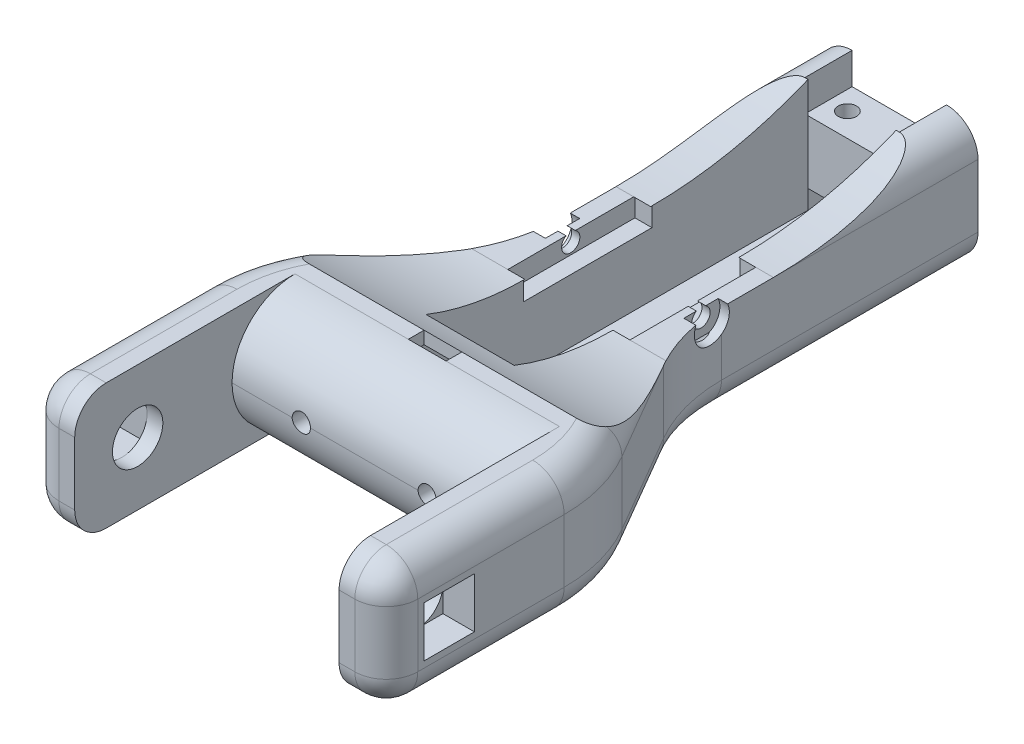
SolidWorks part; units mm, degrees
ref_plane "Спереди" through (0, 0, 0) normal (0, 0, 1) x (1, 0, 0)
ref_plane "Сверху" through (0, 0, 0) normal (0, 1, 0) x (1, 0, 0)
ref_plane "Справа" through (0, 0, 0) normal (1, 0, 0) x (0, 0, -1)
sketch "Эскиз1" plane through (0, 0, 0) normal (0, 1, 0) x (1, 0, 0)
  line L1 (21, 25) -> (-21, 25)
  line L2 (-21, 25) -> (-21, 0)
  line L3 (-21, 0) -> (-28.5, 0)
  line L4 (-28.5, 0) -> (-28.5, 35)
  line L5 (-28.5, 35) -> (-12.5, 62.5)
  line L6 (-12.5, 62.5) -> (-12.5, 110)
  line L7 (-12.5, 110) -> (12.5, 110)
  line L12 (0, -1000) -> (0, 49000) construction
  line L13 (12.5, 62.5) -> (12.5, 110)
  line L14 (28.5, 35) -> (12.5, 62.5)
  line L15 (28.5, 0) -> (28.5, 35)
  line L16 (21, 0) -> (28.5, 0)
  line L17 (21, 25) -> (21, 0)
  point P13 (-24.75, 0)
  point P15 (0, 110)
  point P16 (0, 25)
  dimension "D1" = 21
  dimension "D2" = 7.5
  dimension "D3" = 25
  dimension "D4" = 10
  dimension "D5" = 110
  dimension "D6" = 12.5
  dimension "D7" = 47.5
extrude "Бобышка-Вытянуть1" add sketch "Эскиз1" along normal blind 20
sketch "Эскиз2" plane through (28.5, 0, 0) normal (1, 0, 0) x (0, 0, -1)
  line L0 (-1000, 10) -> (49000, 10) construction
  line L1 (0, 20) -> (0, 0) construction
  line L2 (10, -980) -> (10, 49020) construction
  circle A0 centre (10, 10) radius 4
  point P5 (0, 10)
  dimension "D1" = 8
  dimension "D2" = 10
extrude "Вырез-Вытянуть1" cut sketch "Эскиз2" against normal blind 52
fillet "Скругление1" radius 25 4 edges at (-28.5, 10, -35) (-12.5, 10, -62.5) (28.5, 10, -35) (12.5, 10, -62.5)
fillet "Скругление2" radius 5 26 edges at (-28.5, 20, -14.1282) (-27.6373, 20, -34.7673) (-20.5, 20, -48.75) (-13.3627, 20, -62.7327) (-28.5, 0, -14.1282) (-27.6373, 0, -34.7673) (-20.5, 0, -48.75) (-13.3627, 0, -62.7327) (28.5, 0, -14.1282) (27.6373, 0, -34.7673) (20.5, 0, -48.75) (13.3627, 0, -62.7327) (28.5, 20, -14.1282) (27.6373, 20, -34.7673) (20.5, 20, -48.75) (13.3627, 20, -62.7327) (-24.75, 0, 0) (-24.75, 20, 0) (-28.5, 10, 0) (-12.5, 20, -89.6218) (-12.5, 0, -89.6218) (28.5, 10, 0) (24.75, 0, 0) (24.75, 20, 0) (12.5, 0, -89.6218) (12.5, 20, -89.6218)
fillet "Скругление3" radius 10 2 edges at (0, 0, -25) (0, 20, -25)
sketch "Эскиз4" plane through (28.5, 0, 0) normal (1, 0, 0) x (0, 0, -1)
  line L1 (6, 6) -> (14, 6)
  line L2 (6, 6) -> (6, 14)
  line L3 (6, 14) -> (14, 14)
  line L4 (14, 6) -> (14, 14)
  line L5 (6, 6) -> (14, 14) construction
  line L6 (6, 14) -> (14, 6) construction
  point P0 (10, 10)
  dimension "D1" = 8
extrude "Вырез-Вытянуть2" cut sketch "Эскиз4" against normal blind 5
extrude "Вырез-Вытянуть3" cut sketch "Эскиз4<2>" along normal blind 5 from vertex starting at point (-28.5, 5, -5)
sketch "Эскиз4<2>" plane through (28.5, 0, 0) normal (1, 0, 0) x (0, 0, -1) same geometry as "Эскиз4"
sketch "Эскиз5" plane through (0, 0, -110) normal (0, 0, -1) x (-1, 0, 0)
  line L1 (-7.5, 20) -> (7.5, 20)
  line L2 (-7.5, 20) -> (-7.5, 15)
  line L3 (-7.5, 15) -> (7.5, 15)
  line L4 (7.5, 20) -> (7.5, 15)
  line L5 (-7.5, 0) -> (7.5, 0)
  line L6 (-7.5, 0) -> (-7.5, 5)
  line L7 (-7.5, 5) -> (7.5, 5)
  line L8 (7.5, 0) -> (7.5, 5)
  dimension "D1" = 5
  dimension "D2" = 5
extrude "Вырез-Вытянуть4" cut sketch "Эскиз5" against normal blind 7.5
sketch "Эскиз6" plane through (0, 15, 0) normal (0, 1, 0) x (1, 0, 0)
  line L0 (-1007.5, 106.25) -> (48992.5, 106.25) construction
  line L1 (-7.5, 102.5) -> (-7.5, 110) construction
  line L2 (0, -880) -> (0, 49120) construction
  line L3 (7.5, 110) -> (-7.5, 110) construction
  line L4 (-7.5, 110) -> (-7.5, 102.5) construction
  circle A0 centre (-4.5, 106.25) radius 1.45
  circle A1 centre (4.5, 106.25) radius 1.45
  point P5 (-7.5, 106.25)
  point P10 (0, 110)
  dimension "D1" = 2.9
  dimension "D2" = 3
extrude "Вырез-Вытянуть5" cut sketch "Эскиз6" against normal blind 10
sketch "Эскиз8" plane through (0, 0, 0) normal (1, 0, 0) x (0, 0, -1)
  line L0 (110, 15) -> (110, 5) construction
  line L1 (102.5, 18) -> (37.5, 18)
  line L2 (102.5, 18) -> (102.5, 2)
  line L3 (102.5, 2) -> (37.5, 2)
  line L5 (69.2436, 20) -> (102.5, 20) construction
  line L6 (102.5, 0) -> (69.2436, 0) construction
  arc A0 (37.5, 2) -> (37.5, 18) centre (37.5, 10) cw
  dimension "D1" = 7.5
  dimension "D2" = 2
  dimension "D3" = 2
  dimension "D4" = 65
extrude "Вырез-Вытянуть6" cut sketch "Эскиз8" against normal mid plane 14
sketch "Эскиз9" plane through (0, 0, -110) normal (0, 0, -1) x (-1, 0, 0)
  line L0 (-1012.5, 10) -> (48987.5, 10) construction
  line L1 (-12.5, 15) -> (-12.5, 5) construction
  line L2 (-10, -990) -> (-10, 49010) construction
  line L3 (10, -990) -> (10, 49010) construction
  line L4 (-12.5, 15) -> (-12.5, 5) construction
  line L5 (12.5, 5) -> (12.5, 15) construction
  circle A0 centre (-10, 10) radius 1.45
  circle A1 centre (10, 10) radius 1.45
  point P5 (-12.5, 10)
  dimension "D3" = 2.9
  dimension "D1" = 2.5
  dimension "D2" = 2.5
extrude "Вырез-Вытянуть7" cut sketch "Эскиз9" against normal blind 90
sketch "Эскиз10" plane through (0, 0, 0) normal (1, 0, 0) x (0, 0, -1)
  line L0 (102.5, 20) -> (110, 20) construction
  line L1 (69.2436, 20) -> (102.5, 20) construction
  line L2 (110, 15) -> (69.2436, 15) construction
  line L3 (38.3143, 20) -> (54.1567, 20) construction
  line L4 (56.6712, 15) -> (40.8288, 15) construction
  line L5 (37.5, 20) -> (102.5, 20)
  line L6 (77.5, 15) -> (57.5, 15)
  line L7 (110, 15) -> (110, 5) construction
  arc A0 (102.5, 20) -> (77.5, 15) centre (77.5, 80) cw
  arc A1 (37.5, 20) -> (57.5, 15) centre (57.5, 57.5) ccw
  dimension "D1" = 7.5
  dimension "D4" = 25
  dimension "D2" = 65
  dimension "D3" = 20
extrude "Вырез-Вытянуть8" cut sketch "Эскиз10" against normal through all both and the other way through all
sketch "Эскиз11" plane through (0, 0, -102.5) normal (0, 0, -1) x (-1, 0, 0)
  line L0 (-7, 15) -> (-7, 18) construction
  line L1 (-7, 18) -> (7, 18)
  line L2 (-7, 18) -> (-7, 20)
  line L3 (-7, 20) -> (7, 20)
  line L4 (7, 18) -> (7, 20)
  line L5 (7, 18) -> (-7, 18) construction
  line L6 (7, 18) -> (7, 2) construction
  line L7 (7.5, 20) -> (-7.5, 20) construction
extrude "Вырез-Вытянуть9" cut sketch "Эскиз11" against normal blind 10
sketch "Эскиз12" plane through (0, 20, 0) normal (0, 1, 0) x (1, 0, 0)
  line L0 (-21.2357, 37.5) -> (21.2357, 37.5) construction
  line L1 (-3, 37.5) -> (3, 37.5)
  line L2 (-3, 37.5) -> (-3, 35)
  line L3 (-3, 35) -> (3, 35)
  line L4 (3, 37.5) -> (3, 35)
  line L5 (-21, 35) -> (21, 35) construction
  point P8 (0, 37.5)
  dimension "D1" = 6
extrude "Вырез-Вытянуть10" cut sketch "Эскиз12" against normal blind 10
sketch "Эскиз13" plane through (0, 15, 0) normal (0, 1, 0) x (1, 0, 0)
  line L1 (7, 77.7) -> (9.7, 77.7)
  line L2 (7, 77.7) -> (7, 57.3)
  line L3 (7, 57.3) -> (9.7, 57.3)
  line L4 (9.7, 77.7) -> (9.7, 57.3)
  line L5 (-7, 37.5) -> (-7, 102.5) construction
  line L6 (-7, 77.7) -> (-9.7, 77.7)
  line L7 (-7, 77.7) -> (-7, 57.3)
  line L8 (-7, 57.3) -> (-9.7, 57.3)
  line L9 (-9.7, 77.7) -> (-9.7, 57.3)
  line L12 (-7, 77.5) -> (-7, 102.5) construction
  line L13 (-12.5, 77.5) -> (-7, 77.5) construction
  line L14 (7, 37.5) -> (7, 102.5) construction
  line L15 (-15.4299, 57.5) -> (-7, 57.5) construction
  dimension "D1" = 2.7
  dimension "D2" = 2.7
  dimension "D3" = 0.2
  dimension "D4" = 0.2
extrude "Вырез-Вытянуть11" cut sketch "Эскиз13" against normal blind 3
sketch "Эскиз14" plane through (-9.7, 0, 0) normal (1, 0, 0) x (0, 0, -1)
  line L0 (-936.7638, 13.75) -> (49063.2362, 13.75) construction
  line L1 (77.7, 12) -> (57.3, 12) construction
  line L2 (67.5, -985) -> (67.5, 49015) construction
  line L3 (77.5, 15) -> (57.5, 15) construction
  circle A0 centre (67.5, 13.75) radius 1.45
  point P9 (67.5, 15)
  dimension "D2" = 2.9
  dimension "D1" = 1.75
extrude "Вырез-Вытянуть12" cut sketch "Эскиз14" along normal through all both and the other way through all
sketch "Эскиз15" plane through (12.5, 0, 0) normal (1, 0, 0) x (0, 0, -1)
  circle A0 centre (67.5, 13.75) radius 3
  circle A1 centre (67.5, 13.75) radius 1.45 construction
  dimension "D1" = 6
extrude "Вырез-Вытянуть13" cut sketch "Эскиз15" against normal blind 1.5 and the other way through all
extrude "Вырез-Вытянуть14" cut sketch "Эскиз15<2>" along normal blind 1.5 and the other way through all from vertex starting at point (-12.5, 15, -77.5)
sketch "Эскиз15<2>" plane through (12.5, 0, 0) normal (1, 0, 0) x (0, 0, -1) same geometry as "Эскиз15"
ref_plane "Плоскость1" through (0, 10, 0) normal (0, 1, 0) x (1, 0, 0)
